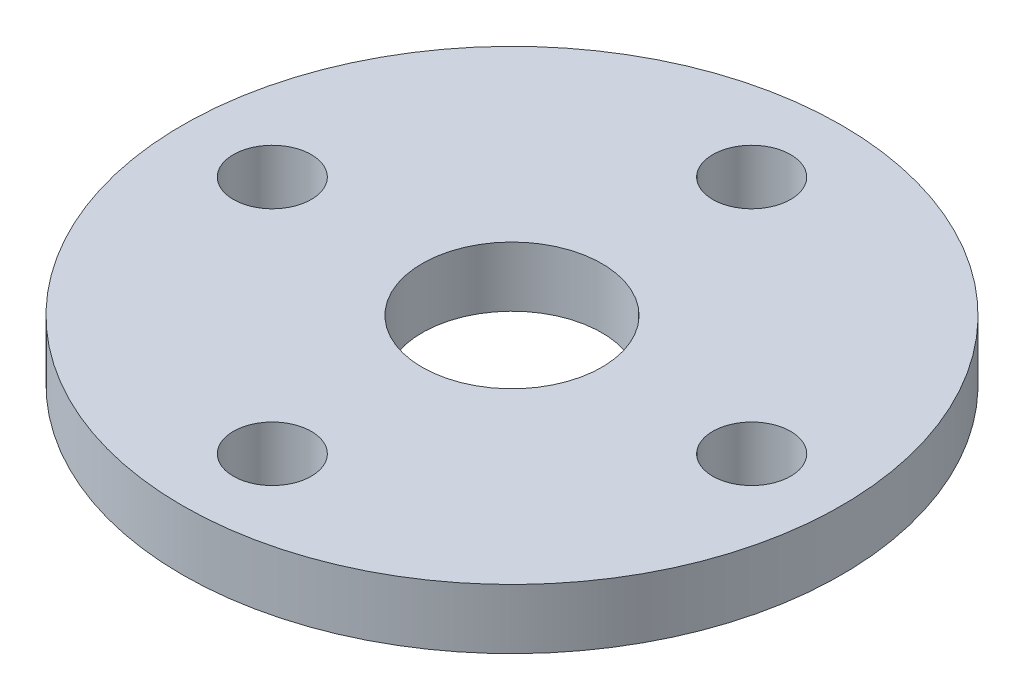
SolidWorks part; units mm, degrees
ref_plane "前基準面" through (0, 0, 0) normal (0, 0, 1) x (1, 0, 0)
ref_plane "上基準面" through (0, 0, 0) normal (0, 1, 0) x (1, 0, 0)
ref_plane "右基準面" through (0, 0, 0) normal (1, 0, 0) x (0, 0, -1)
sketch "草圖1" plane through (0, 0, 0) normal (0, 1, 0) x (1, 0, 0)
  line L0 (0, 0) -> (0, 8) construction
  line L1 (0, 0) -> (8, 0) construction
  line L2 (0, 0) -> (0, -8) construction
  line L3 (0, 0) -> (-8, 0) construction
  circle A0 centre (0, 0) radius 11
  circle A1 centre (0, 8) radius 1.3
  circle A2 centre (8, 0) radius 1.3
  circle A3 centre (0, -8) radius 1.3
  circle A4 centre (-8, 0) radius 1.3
  circle A5 centre (0, 0) radius 3
  point P14 (0, 0)
  dimension "D1" = 22
  dimension "D3" = 2.6
  dimension "D5" = 6
  dimension "D2" = 8
  dimension "D4" = 4
extrude "填料-伸長1" add sketch "草圖1" along normal blind 2
